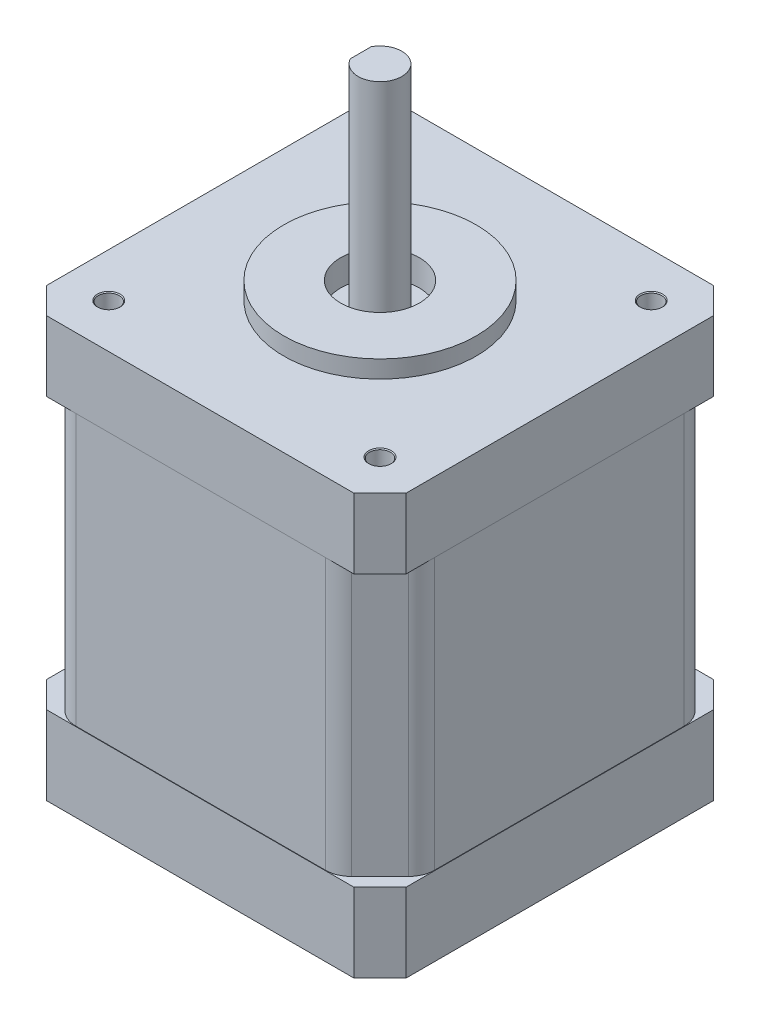
SolidWorks part; units mm, degrees
ref_plane "Alzado" through (0, 0, 0) normal (0, 0, 1) x (1, 0, 0)
ref_plane "Planta" through (0, 0, 0) normal (0, 1, 0) x (1, 0, 0)
ref_plane "Vista lateral" through (0, 0, 0) normal (1, 0, 0) x (0, 0, -1)
sketch "Croquis1" plane through (0, 0, 0) normal (0, 1, 0) x (1, 0, 0)
  line L1 (-20.5, 20.5) -> (20.5, 20.5)
  line L2 (-20.5, 20.5) -> (-20.5, -20.5)
  line L3 (-20.5, -20.5) -> (20.5, -20.5)
  line L4 (20.5, 20.5) -> (20.5, -20.5)
  line L5 (-20.5, 20.5) -> (20.5, -20.5) construction
  line L6 (-20.5, -20.5) -> (20.5, 20.5) construction
  point P0 (0, 0)
  dimension "D1" = 41
  dimension "D2" = 41
extrude "Saliente-Extruir1" add sketch "Croquis1" along normal mid plane 31
chamfer "Chaflán1" distance 5 angle 45 4 edges at (-20.5, 0, 20.5) (-20.5, 0, -20.5) (20.5, 0, -20.5) (20.5, 0, 20.5)
fillet "Redondeo1" radius 3 8 edges at (15.5, 0, 20.5) (20.5, 0, 15.5) (20.5, 0, -15.5) (15.5, 0, -20.5) (-15.5, 0, 20.5) (-20.5, 0, 15.5) (-20.5, 0, -15.5) (-15.5, 0, -20.5)
sketch "Croquis2" plane through (0, 15.5, 0) normal (0, 1, 0) x (1, 0, 0)
  line L1 (-20.55, -20.55) -> (20.55, -20.55)
  line L2 (-20.55, -20.55) -> (-20.55, 20.55)
  line L3 (-20.55, 20.55) -> (20.55, 20.55)
  line L4 (20.55, -20.55) -> (20.55, 20.55)
  line L5 (-20.55, -20.55) -> (20.55, 20.55) construction
  line L6 (-20.55, 20.55) -> (20.55, -20.55) construction
  point P0 (0, 0)
  dimension "D1" = 41.1
extrude "Saliente-Extruir2" add sketch "Croquis2" along normal blind 8
chamfer "Chaflán2" distance 3 angle 45 4 edges at (20.55, 19.5, 20.55) (-20.55, 19.5, 20.55) (20.55, 19.5, -20.55) (-20.55, 19.5, -20.55)
sketch "Croquis3" plane through (0, -15.5, 0) normal (0, -1, 0) x (1, 0, 0)
  line L8 (17.55, 20.55) -> (-17.55, 20.55)
  line L9 (20.55, 17.55) -> (17.55, 20.55)
  line L10 (20.55, -17.55) -> (20.55, 17.55)
  line L11 (17.55, -20.55) -> (20.55, -17.55)
  line L12 (-17.55, -20.55) -> (17.55, -20.55)
  line L13 (-20.55, -17.55) -> (-17.55, -20.55)
  line L14 (-20.55, 17.55) -> (-20.55, -17.55)
  line L15 (-17.55, 20.55) -> (-20.55, 17.55)
  line L16 (17.55, 20.55) -> (-17.55, 20.55)
  line L17 (20.55, 17.55) -> (17.55, 20.55)
  line L18 (20.55, -17.55) -> (20.55, 17.55)
  line L19 (17.55, -20.55) -> (20.55, -17.55)
  line L20 (-17.55, -20.55) -> (17.55, -20.55)
  line L21 (-20.55, -17.55) -> (-17.55, -20.55)
  line L22 (-20.55, 17.55) -> (-20.55, -17.55)
  line L23 (-17.55, 20.55) -> (-20.55, 17.55)
  dimension "D1" = 0
extrude "Saliente-Extruir3" add sketch "Croquis3" along normal blind 9
sketch "Croquis4" plane through (0, 23.5, 0) normal (0, 1, 0) x (1, 0, 0)
  circle A0 centre (0, 0) radius 11
  dimension "D1" = 22
extrude "Saliente-Extruir4" add sketch "Croquis4" along normal blind 2
sketch "Croquis5" plane through (0, 23.5, 0) normal (0, 1, 0) x (1, 0, 0)
  line L1 (-20.55, 17.55) -> (-20.55, -17.55) construction
  line L4 (0, 0) -> (26.1113, 0) construction
  circle A0 centre (-15.5, 15.5) radius 1.1906
  circle A1 centre (15.5, 15.5) radius 1.1906
  circle A2 centre (15.5, -15.5) radius 1.1906
  circle A3 centre (-15.5, -15.5) radius 1.1906
  dimension "D4" = 2.3813
  dimension "D1" = 31
  dimension "D2" = 15.5
  dimension "D3" = 5.05
extrude "Cortar-Extruir1" cut sketch "Croquis5" against normal blind 3.175
chamfer "Chaflán3" distance 0.1 angle 45 4 edges at (-15.5, 23.5, 14.3094) (15.5, 23.5, 14.3094) (15.5, 23.5, -14.3094) (-15.5, 23.5, -14.3094)
sketch "Croquis6" plane through (0, -24.5, 0) normal (0, -1, 0) x (1, 0, 0)
  circle A0 centre (0, 0) radius 4.7625
  circle A1 centre (-15.5, 15.5) radius 1.2906 construction
  circle A2 centre (-15.5, 15.5) radius 1.2906 construction
  circle A3 centre (-15.5, 15.5) radius 3.175
  circle A4 centre (15.5, 15.5) radius 3.175
  circle A5 centre (15.5, -15.5) radius 3.175
  circle A6 centre (-15.5, -15.5) radius 3.175
  point P16 (0, 0)
  dimension "D1" = 9.525
  dimension "D2" = 6.35
  dimension "D3" = 4
extrude "Cortar-Extruir2" cut sketch "Croquis6" against normal blind 3
dome "Cúpula1" faces to dome 1 distance 3 reverse direction no elliptical dome no face at (15.5, -21.5, 12.325) parameters "D1"=3
dome "Cúpula2" faces to dome 1 distance 3 reverse direction no elliptical dome no face at (-15.5, -21.5, 12.325) parameters "D1"=3
dome "Cúpula3" faces to dome 1 distance 3 reverse direction no elliptical dome no face at (15.5, -21.5, -18.675) parameters "D1"=3
dome "Cúpula4" faces to dome 1 distance 3 reverse direction no elliptical dome no face at (-15.5, -21.5, -18.675) parameters "D1"=3
sketch "Croquis7" plane through (0, 25.5, 0) normal (0, 1, 0) x (1, 0, 0)
  circle A0 centre (0, 0) radius 4.5
  dimension "D1" = 9
extrude "Cortar-Extruir3" cut sketch "Croquis7" against normal blind 3
sketch "Croquis8" plane through (0, 22.5, 0) normal (0, 1, 0) x (1, 0, 0)
  line L0 (-2.2, 1.1874) -> (-2.2, -1.1874)
  circle A0 centre (0, 0) radius 2.5
  point P5 (2.5, 0)
  dimension "D1" = 5
  dimension "D2" = 4.7
extrude "Saliente-Extruir5" add sketch "Croquis8" along normal blind 24.4312 contours L0 A0 | L0 A0 region at (0.0583, 22.5, 0) region at (-2.3206, 22.5, 0)
sketch "Croquis9" plane through (0, 46.9312, 0) normal (0, 1, 0) x (1, 0, 0)
  line L0 (-2.2, 1.1874) -> (-2.2, -1.1874) construction
  line L1 (-2.2, 1.1874) -> (-2.2, -1.1874)
  circle A0 centre (0, 0) radius 2.5 construction
  circle A1 centre (0, 0) radius 2.5
  circle M1 centre (0, 0) radius 2.5
extrude "Cortar-Extruir4" cut sketch "Croquis9" against normal blind 20.5 contours L1 M1 region at (-2.3206, 46.9312, 0)
